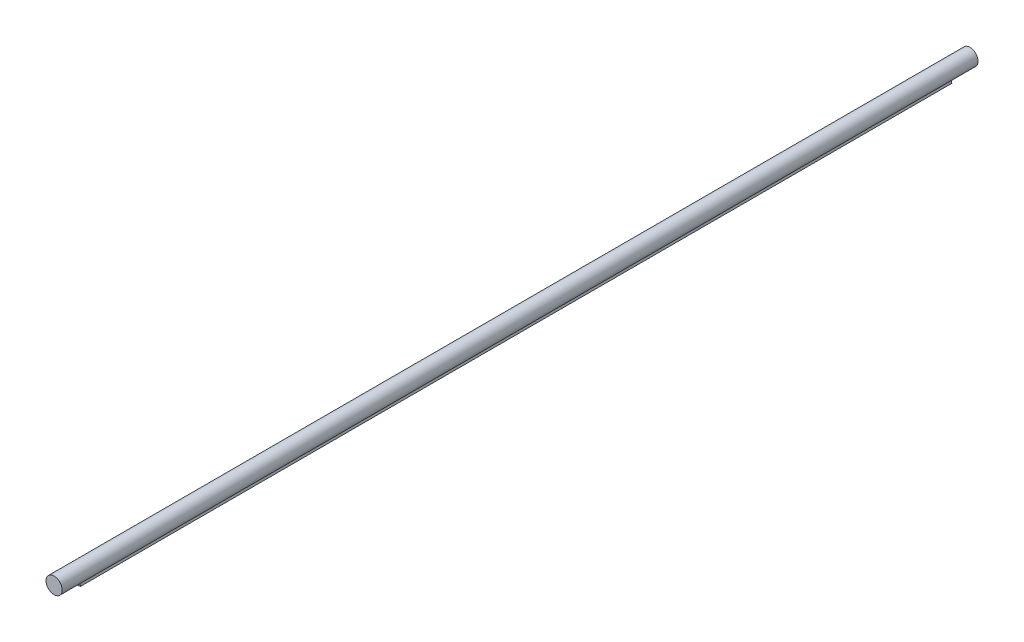
SolidWorks part; units mm, degrees
note: The reader was unsure of these and kept them because the rebuilt part matched: shared geometry of "Sketch2<2>".
ref_plane "Front Plane" through (0, 0, 0) normal (0, 0, 1) x (1, 0, 0)
ref_plane "Top Plane" through (0, 0, 0) normal (0, 1, 0) x (1, 0, 0)
ref_plane "Right Plane" through (0, 0, 0) normal (1, 0, 0) x (0, 0, -1)
sketch "Sketch1" plane through (0, 0, 0) normal (0, 0, 1) x (1, 0, 0)
  line L0 (4.0351, -9.7911) -> (3.5863, -7.0811) construction
  line L1 (-0.6634, -10.5691) -> (4.0351, -9.7911) construction
  line L2 (-1.1122, -7.8592) -> (-0.6634, -10.5691) construction
  line L3 (4.0351, -9.7911) -> (3.5863, -7.0811)
  line L4 (-0.6634, -10.5691) -> (4.0351, -9.7911)
  line L5 (-1.1122, -7.8592) -> (-0.6634, -10.5691)
  circle A0 centre (0, 0) radius 7.9375 construction
  arc A2 (3.5863, -7.0811) -> (-1.1122, -7.8592) centre (0, 0) ccw
  dimension "D1" = 15.875
extrude "Boss-Extrude1" add sketch "Sketch1" along normal up to surface (898.1281 mm away) from surface at -68.0641
sketch "Sketch2" plane through (0, 0, 830.0641) normal (0, 0, 1) x (1, 0, 0)
  circle A0 centre (0, 0) radius 7.9375
  circle A1 centre (0, 0) radius 10.5899
  arc A2 (3.5863, -7.0811) -> (-1.1122, -7.8592) centre (0, 0) ccw construction
extrude "Cut-Extrude1" cut sketch "Sketch2" against normal up to surface (21.8281 mm away)
ref_plane "Plane1" through (0, 0, 381) normal (0, 0, -1) x (-1, 0, 0)
extrude "Cut-Extrude2" cut sketch "Sketch2<2>" against normal up to surface (21.8281 mm away) from surface
sketch "Sketch2<2>" plane through (0, 0, 830.0641) normal (0, 0, 1) x (1, 0, 0) same geometry as "Sketch2"
